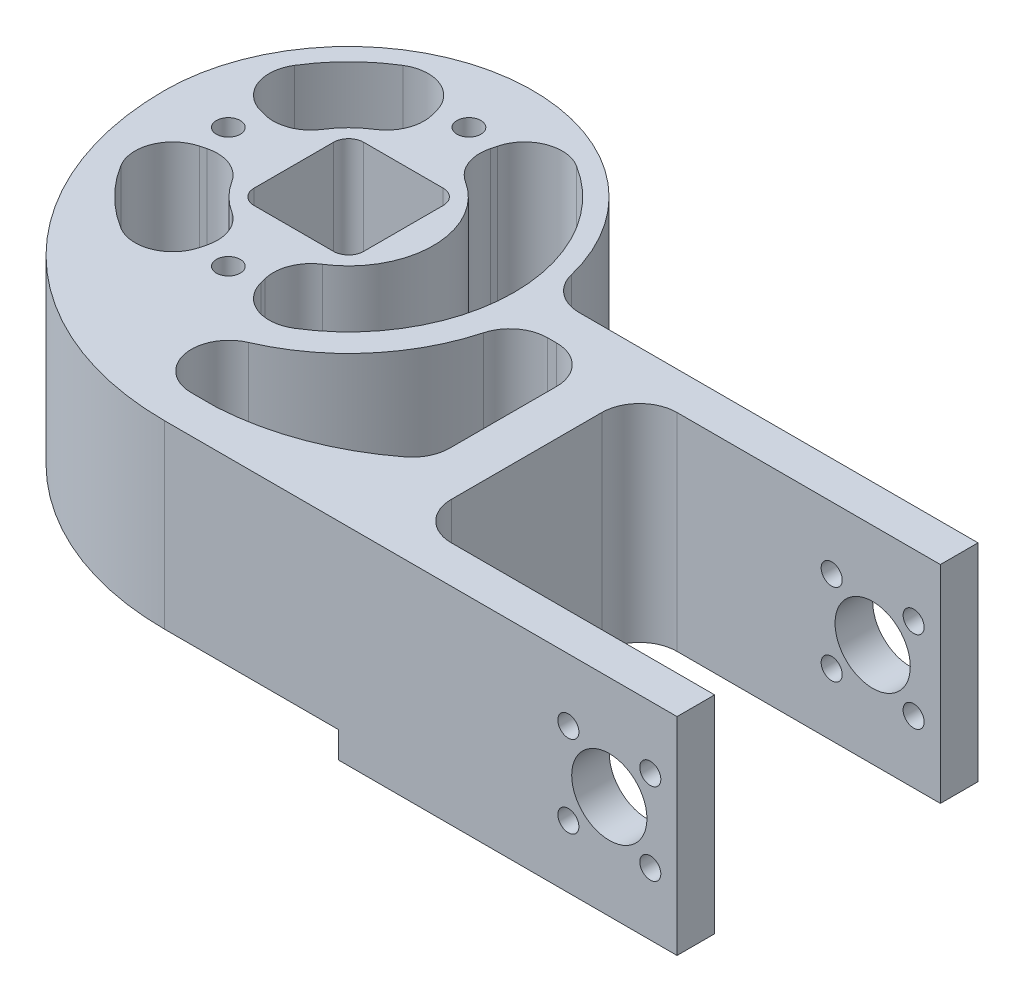
SolidWorks part; units mm, degrees
material "6061-T6 (SS)"
ref_plane "Front Plane" through (0, 0, 0) normal (0, 0, 1) x (1, 0, 0)
ref_plane "Top Plane" through (0, 0, 0) normal (0, 1, 0) x (1, 0, 0)
ref_plane "Right Plane" through (0, 0, 0) normal (1, 0, 0) x (0, 0, -1)
sketch "Sketch1" plane through (0, 0, 0) normal (0, 1, 0) x (1, 0, 0)
  circle A0 centre (0, 0) radius 31.0896
  dimension "D1" = 62.1792
extrude "Boss-Extrude1" add sketch "Sketch1" along normal blind 34.925
sketch "Sketch2" plane through (0, 34.925, 0) normal (0, 1, 0) x (1, 0, 0)
  line L0 (0, 0) -> (-31.0896, 0) construction
  line L1 (0, 0) -> (30.9857, 2.54) construction
  line L2 (46.5427, -48.26) -> (17.1704, -48.26)
  line L4 (46.5427, -48.26) -> (46.5427, 2.54)
  line L7 (30.9857, 2.54) -> (46.5427, 2.54)
  circle A0 centre (0, 0) radius 31.0896 construction
  arc A1 (17.1704, -48.26) -> (-31.0896, 0) centre (17.1704, 0) cw
  circle A2 centre (0, 0) radius 31.0896
  arc A3 (-31.0896, 0) -> (30.9857, 2.54) centre (0, 0) ccw
  dimension "D3" = 2.54
  dimension "D1" = 50.8
  dimension "D2" = 15.557
  dimension "D4" = 0
extrude "Boss-Extrude2" add sketch "Sketch2" against normal blind 30.48
sketch "Sketch3" plane through (0, 34.925, 0) normal (0, 1, 0) x (1, 0, 0)
  line L0 (46.5427, -0.3336) -> (46.5427, -48.26)
  line L1 (17.1704, -48.26) -> (46.5427, -48.26) construction
  line L2 (46.5427, -48.26) -> (103.6927, -48.26)
  line L3 (103.6927, -48.26) -> (103.6927, -41.91)
  line L4 (103.6927, -41.91) -> (52.8927, -41.91)
  line L5 (52.8927, -41.91) -> (52.8927, -3.81)
  line L6 (52.8927, -3.81) -> (103.6927, -3.81)
  line L7 (103.6927, -3.81) -> (103.6927, 2.54)
  line L8 (103.6927, 2.54) -> (46.5427, 2.54)
  line L9 (46.5427, -0.3336) -> (46.5427, 2.54)
  line L10 (46.5427, -48.26) -> (46.5427, 2.54) construction
  dimension "D1" = 57.15
  dimension "D2" = 38.1
  dimension "D3" = 6.35
  dimension "D4" = 6.35
extrude "Boss-Extrude3" add sketch "Sketch3" against normal up to surface (34.925 mm away) up to face at (0, 0, 31.0896)
sketch "Sketch4" plane through (0, 0, -2.54) normal (0, 0, -1) x (-1, 0, 0)
  line L0 (-103.6927, 17.4625) -> (-92.2627, 17.4625) construction
  line L1 (-103.6927, 0) -> (-103.6927, 34.925) construction
  line L2 (-92.2627, 17.4625) -> (-99.1775, 10.5477) construction
  line L3 (-92.2627, 17.4625) -> (-99.1775, 24.3773) construction
  line L4 (-92.2627, 17.4625) -> (-99.1775, 10.5477) construction
  line L5 (-92.2627, 17.4625) -> (-85.3479, 10.5477) construction
  line L6 (-92.2627, 17.4625) -> (-85.3479, 24.3773) construction
  line L8 (-99.1775, 24.3773) -> (-103.6927, 24.3773) construction
  line L9 (-103.6927, 0) -> (-103.6927, 34.925) construction
  line L10 (-99.1775, 10.5477) -> (-103.6927, 10.5477) construction
  circle A0 centre (-92.2627, 17.4625) radius 6.35
  circle A1 centre (-85.3479, 10.5477) radius 1.778
  circle A3 centre (-99.1775, 24.3773) radius 1.778
  circle A4 centre (-99.1775, 10.5477) radius 1.778
  circle A5 centre (-85.3479, 24.3773) radius 1.778
  dimension "D1" = 11.43
  dimension "D2" = 12.7
  dimension "D3" = 3.556
  dimension "D5" = 19.558
  dimension "D4" = 19.558
extrude "Cut-Extrude1" cut sketch "Sketch4" against normal up to surface (50.8 mm away) up to face at (53.3542, 12.7529, 48.26)
sketch "Sketch5" plane through (0, 34.925, 0) normal (0, 1, 0) x (1, 0, 0)
  line L1 (-9.2497, 9.2497) -> (9.2497, 9.2497)
  line L2 (-9.2497, 9.2497) -> (-9.2497, -9.2497)
  line L3 (-9.2497, -9.2497) -> (9.2497, -9.2497)
  line L4 (9.2497, 9.2497) -> (9.2497, -9.2497)
  line L5 (-9.2497, 9.2497) -> (9.2497, -9.2497) construction
  line L6 (-9.2497, -9.2497) -> (9.2497, 9.2497) construction
  point P0 (0, 0)
  dimension "D1" = 26.162
extrude "Cut-Extrude2" cut sketch "Sketch5" against normal up to surface (34.925 mm away) up to face at (0, 0, 31.0896)
fillet "Fillet3" radius 2.54 1 edges at (-9.2497, 17.4625, 9.2497)
fillet "Fillet4" radius 2.54 1 edges at (-9.2497, 17.4625, -9.2497)
fillet "Fillet5" radius 2.54 1 edges at (9.2497, 17.4625, -9.2497)
fillet "Fillet6" radius 2.54 1 edges at (9.2497, 17.4625, 9.2497)
fillet "Fillet8" radius 6.35 1 edges at (30.9857, 19.685, -2.54)
fillet "Fillet9" radius 6.35 1 edges at (52.8927, 17.4625, 41.91)
fillet "Fillet10" radius 6.35 1 edges at (52.8927, 17.4625, 3.81)
sketch "Sketch6" plane through (0, 34.925, 0) normal (0, 1, 0) x (1, 0, 0)
  line L7 (103.6927, 2.54) -> (36.3688, 2.54)
  line L8 (17.1704, -48.26) -> (103.6927, -48.26)
  line L9 (103.6927, -48.26) -> (103.6927, -41.91)
  line L10 (103.6927, -41.91) -> (59.2427, -41.91)
  line L11 (52.8927, -35.56) -> (52.8927, -10.16)
  line L12 (59.2427, -3.81) -> (103.6927, -3.81)
  line L13 (103.6927, -3.81) -> (103.6927, 2.54)
  line L14 (103.6927, 2.54) -> (36.3688, 2.54)
  line L15 (17.1704, -48.26) -> (103.6927, -48.26)
  line L16 (103.6927, -48.26) -> (103.6927, -41.91)
  line L17 (103.6927, -41.91) -> (59.2427, -41.91)
  line L18 (52.8927, -35.56) -> (52.8927, -10.16)
  line L19 (59.2427, -3.81) -> (103.6927, -3.81)
  line L20 (103.6927, -3.81) -> (103.6927, 2.54)
  line L35 (59.2427, -0.635) -> (36.3688, -0.635)
  line L36 (17.1704, -45.085) -> (59.2427, -45.085)
  line L37 (49.7177, -35.56) -> (49.7177, -10.16)
  line L38 (43.6884, -0.635) -> (36.3688, -0.635)
  line L39 (17.1704, -45.085) -> (43.6884, -45.085)
  line L40 (49.7177, -35.56) -> (49.7177, -10.16)
  arc A5 (30.2004, 7.3822) -> (36.3688, 2.54) centre (36.3688, 8.89) ccw
  arc A6 (30.2004, 7.3822) -> (-31.0896, 0) centre (0, 0) ccw
  arc A7 (-31.0896, 0) -> (17.1704, -48.26) centre (17.1704, 0) ccw
  arc A8 (52.8927, -35.56) -> (59.2427, -41.91) centre (59.2427, -35.56) ccw
  arc A9 (59.2427, -3.81) -> (52.8927, -10.16) centre (59.2427, -10.16) ccw
  arc A10 (30.2004, 7.3822) -> (36.3688, 2.54) centre (36.3688, 8.89) ccw
  arc A11 (30.2004, 7.3822) -> (-31.0896, 0) centre (0, 0) ccw
  arc A12 (-31.0896, 0) -> (17.1704, -48.26) centre (17.1704, 0) ccw
  arc A13 (52.8927, -35.56) -> (59.2427, -41.91) centre (59.2427, -35.56) ccw
  arc A14 (59.2427, -3.81) -> (52.8927, -10.16) centre (59.2427, -10.16) ccw
  arc A20 (43.6884, -0.635) -> (49.9101, -8.255) centre (43.6884, -6.985) cw
  arc A21 (43.6884, -45.085) -> (49.9101, -37.465) centre (43.6884, -38.735) ccw
  arc A25 (27.1162, 6.6283) -> (36.3688, -0.635) centre (36.3688, 8.89) ccw
  arc A26 (27.1162, 6.6283) -> (-27.9146, 0) centre (0, 0) ccw
  arc A27 (-27.9146, 0) -> (17.1704, -45.085) centre (17.1704, 0) ccw
  arc A28 (49.7177, -35.56) -> (59.2427, -45.085) centre (59.2427, -35.56) ccw
  arc A29 (59.2427, -0.635) -> (49.7177, -10.16) centre (59.2427, -10.16) ccw
  arc A30 (27.1162, 6.6283) -> (36.3688, -0.635) centre (36.3688, 8.89) ccw
  arc A31 (27.1162, 6.6283) -> (-27.9146, 0) centre (0, 0) ccw
  arc A32 (-27.9146, 0) -> (17.1704, -45.085) centre (17.1704, 0) ccw
  arc A33 (49.7177, -35.56) -> (49.9101, -37.465) centre (59.2427, -35.56) ccw
  arc A34 (49.9101, -8.255) -> (49.7177, -10.16) centre (59.2427, -10.16) ccw
  line M21 (9.2497, 6.7097) -> (9.2497, -6.7097)
  arc M22 (9.2497, -6.7097) -> (6.7097, -9.2497) centre (6.7097, -6.7097) cw
  line M23 (6.7097, -9.2497) -> (-6.7097, -9.2497)
  arc M24 (-6.7097, -9.2497) -> (-9.2497, -6.7097) centre (-6.7097, -6.7097) cw
  line M25 (-9.2497, -6.7097) -> (-9.2497, 6.7097)
  arc M26 (-9.2497, 6.7097) -> (-6.7097, 9.2497) centre (-6.7097, 6.7097) cw
  line M27 (-6.7097, 9.2497) -> (6.7097, 9.2497)
  arc M28 (6.7097, 9.2497) -> (9.2497, 6.7097) centre (6.7097, 6.7097) cw
  dimension "D3" = 6.35
  dimension "D1" = 0
  dimension "D2" = 3.175
extrude "Cut-Extrude3" [suppressed] cut sketch "Sketch6" against normal blind 19.05 contours A34 A20 L38 A30 A31 A32 L39 A21 A33 L40 M28 M21 M22 M23 M24 M25 M26 M27
sketch "Sketch8" [suppressed] plane through (0, 15.875, 0) normal (0, 1, 0) x (1, 0, 0)
  line L1 (35.1127, -2.54) -> (41.4627, -2.54)
  line L2 (28.7627, -8.89) -> (28.7627, -36.83)
  line L3 (47.8127, -8.89) -> (47.8127, -36.83)
  line L6 (35.1127, -43.18) -> (41.4627, -43.18)
  line L7 (103.6927, 2.54) -> (36.3688, 2.54) construction
  line L8 (52.8927, -35.56) -> (52.8927, -10.16) construction
  line L9 (17.1704, -48.26) -> (103.6927, -48.26) construction
  arc A0 (28.7627, -36.83) -> (35.1127, -43.18) centre (35.1127, -36.83) ccw
  arc A1 (47.8127, -36.83) -> (41.4627, -43.18) centre (41.4627, -36.83) cw
  arc A2 (41.4627, -2.54) -> (47.8127, -8.89) centre (41.4627, -8.89) cw
  arc A3 (28.7627, -8.89) -> (35.1127, -2.54) centre (35.1127, -8.89) cw
  dimension "D1" = 6.35
  dimension "D2" = 5.08
  dimension "D3" = 5.08
  dimension "D4" = 19.05
  dimension "D5" = 5.08
extrude "Cut-Extrude4" [suppressed] cut sketch "Sketch8" against normal up to surface (11.43 mm away) up to face at (21.5778, 4.445, 25.8461)
sketch "Sketch9" [suppressed] plane through (0, 15.875, 0) normal (0, 1, 0) x (1, 0, 0)
  line L0 (-9.3373, 19.4097) -> (-9.3373, 18.7747)
  line L1 (-2.9873, 12.4247) -> (3.3627, 12.4247)
  line L2 (9.7127, 18.7747) -> (9.7127, 19.4097)
  line L3 (-2.9873, 25.7597) -> (3.3627, 25.7597)
  line L4 (-6.7097, 9.2497) -> (6.7097, 9.2497) construction
  line L5 (28.7627, -11.8013) -> (28.7627, -8.89) construction
  line L6 (-9.2497, -6.7097) -> (-9.2497, 6.7097) construction
  line L7 (9.2497, 6.7097) -> (9.2497, -6.7097) construction
  line L9 (-9.2497, 0) -> (9.2497, 0) construction
  line L10 (9.7127, -18.7747) -> (9.7127, -19.4097)
  line L11 (-2.9873, -12.4247) -> (3.3627, -12.4247)
  line L12 (-9.3373, -19.4097) -> (-9.3373, -18.7747)
  line L13 (-2.9873, -25.7597) -> (3.3627, -25.7597)
  arc A0 (3.3627, 12.4247) -> (9.7127, 18.7747) centre (3.3627, 18.7747) ccw
  arc A1 (-9.3373, 18.7747) -> (-2.9873, 12.4247) centre (-2.9873, 18.7747) ccw
  arc A2 (-9.3373, 19.4097) -> (-2.9873, 25.7597) centre (-2.9873, 19.4097) cw
  arc A3 (9.7127, 19.4097) -> (3.3627, 25.7597) centre (3.3627, 19.4097) ccw
  arc A4 (3.3627, -12.4247) -> (9.7127, -18.7747) centre (3.3627, -18.7747) cw
  arc A5 (-9.3373, -18.7747) -> (-2.9873, -12.4247) centre (-2.9873, -18.7747) cw
  arc A6 (-9.3373, -19.4097) -> (-2.9873, -25.7597) centre (-2.9873, -19.4097) ccw
  arc A7 (9.7127, -19.4097) -> (3.3627, -25.7597) centre (3.3627, -19.4097) cw
  dimension "D1" = 6.35
  dimension "D2" = 3.175
  dimension "D3" = 16.51
  dimension "D4" = 19.05
  dimension "D5" = 19.05
extrude "Cut-Extrude5" [suppressed] cut sketch "Sketch9" against normal up to surface (11.43 mm away) up to face at (21.5778, 4.445, 25.8461)
sketch "Sketch11" plane through (0, 4.445, 0) normal (0, -1, 0) x (-1, 0, 0)
  line L0 (-46.5427, -48.26) -> (-46.5427, 2.54)
  line L1 (-103.6927, -3.81) -> (-32.1601, -3.81)
  line L2 (-103.6927, -41.91) -> (-14.7927, -41.91)
  line L3 (-18.1864, 0) -> (-32.385, 0) construction
  line L4 (-45.2727, -3.81) -> (-45.2727, -31.1827)
  circle A0 centre (0, 0) radius 32.385
  arc A2 (-17.1704, -48.26) -> (31.0896, 0) centre (-17.1704, 0) ccw construction
  circle A3 centre (-17.1704, 0) radius 41.9774
  dimension "D1" = 64.77
  dimension "D3" = 88.9
  dimension "D2" = 14.1986
  dimension "D4" = 1.27
sketch "Sketch12" plane through (0, 0, 0) normal (0, -1, 0) x (1, 0, 0)
  line L0 (0, 0) -> (0, -20.3032) construction
  line L1 (0, 0) -> (0, 20.3032) construction
  line L2 (0, 0) -> (-20.3032, 0) construction
  line L3 (0, 0) -> (20.3032, 0) construction
  circle A0 centre (0, 20.3032) radius 2.0193
  circle A1 centre (-20.3032, 0) radius 2.0193
  circle A2 centre (0, -20.3032) radius 2.0193
  dimension "D1" = 4.0386
extrude "Cut-Extrude7" cut sketch "Sketch12" against normal up to surface (34.925 mm away) up to face at (0, 34.925, 0)
extrude "Cut-Extrude8" cut sketch "Sketch11" against normal through all contours L0 A3 L2 A0 L1 region at (27.27, 4.445, 26.5567)
fillet "Fillet11" radius 6.35 4 edges at (32.1601, 19.685, 3.81) (-12.1864, 19.685, 30.0047) (45.2727, 19.685, 31.1827) (45.2727, 19.685, 3.81)
sketch "Sketch13" plane through (0, 0, 0) normal (0, -1, 0) x (1, 0, 0)
  line L0 (0, 0) -> (6.9908, 27.0513)
  line L1 (0, 0) -> (6.9908, -27.0513)
  line L2 (0, 0) -> (-6.9908, 27.0513)
  line L3 (0, 0) -> (-27.0513, 6.9908)
  line L4 (0, 0) -> (-27.0513, -6.9908)
  line L5 (0, 0) -> (-6.9908, -27.0513)
  circle A0 centre (0, 0) radius 27.94
  circle A1 centre (0, 0) radius 14.2875
  circle A2 centre (0, 20.3032) radius 2.0193 construction
  circle A3 centre (0, -20.3032) radius 2.0193 construction
  circle A4 centre (-20.3032, 0) radius 2.0193 construction
  circle A5 centre (-20.3032, 0) radius 2.0193 construction
  dimension "D1" = 55.88
  dimension "D2" = 28.575
  dimension "D3" = 5.08
  dimension "D4" = 5.08
  dimension "D5" = 5.08
  dimension "D6" = 5.08
  dimension "D7" = 5.08
  dimension "D8" = 5.08
extrude "Cut-Extrude9" cut sketch "Sketch13" against normal through all contours A1 L1 A0 L0 | A1 L2 A0 L3 | A1 L4 A0 L5 region at (16.0516, 0, 0) region at (-14.73, 0, 14.73) region at (-14.73, 0, -14.73)
fillet "Fillet12" radius 6.35 13 edges at (-27.0513, 17.4625, -6.9908) (-13.833, 17.4625, -3.5748) (19.5481, 19.685, 41.91) (-27.0513, 17.4625, 6.9908) (-6.9908, 17.4625, 27.0513) (-3.5748, 17.4625, 13.833) (-13.833, 17.4625, 3.5748) (-6.9908, 17.4625, -27.0513) (-3.5748, 17.4625, -13.833) (6.9908, 17.4625, -27.0513) (3.5748, 17.4625, -13.833) (3.5748, 17.4625, 13.833) (6.9908, 17.4625, 27.0513)
